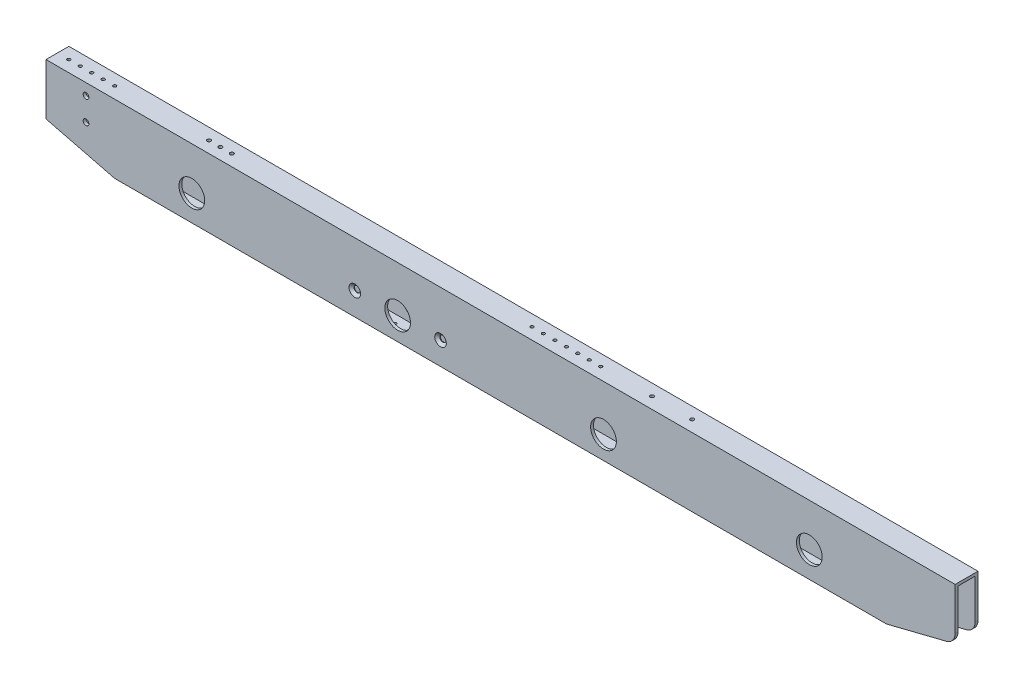
SolidWorks part; units mm, degrees
material "6061-T6 (SS)"
ref_plane "Front Plane" through (0, 0, 0) normal (0, 0, 1) x (1, 0, 0)
ref_plane "Top Plane" through (0, 0, 0) normal (0, 1, 0) x (1, 0, 0)
ref_plane "Right Plane" through (0, 0, 0) normal (1, 0, 0) x (0, 0, -1)
sketch "Sketch1" plane through (0, 0, 0) normal (0, 0, 1) x (1, 0, 0)
  line L0 (0, -12.7) -> (-342.9, -9.525) construction
  line L1 (-504.825, 38.1) -> (504.825, 38.1)
  line L2 (-504.825, 38.1) -> (-504.825, -38.1)
  line L3 (-504.825, -38.1) -> (504.825, -38.1)
  line L4 (504.825, 38.1) -> (504.825, -38.1)
  line L5 (-504.825, 38.1) -> (504.825, -38.1) construction
  line L6 (-504.825, -38.1) -> (504.825, 38.1) construction
  line L7 (-504.825, -38.1) -> (504.825, -38.1) construction
  line L8 (-504.825, -38.1) -> (-504.825, -12.7) construction
  line L9 (-327.025, -63.5) -> (327.025, -63.5) construction
  line L10 (-504.825, -12.7) -> (504.825, -12.7) construction
  line L11 (504.825, -38.1) -> (504.825, -12.7) construction
  line L12 (0, -12.7) -> (342.9, -9.525) construction
  line L13 (-114.3, -12.7) -> (114.3, -12.7) construction
  circle A0 centre (114.3, -12.7) radius 14.2875
  circle A1 centre (-342.9, -9.525) radius 14.2875
  circle A2 centre (342.9, -9.525) radius 14.2875
  circle A3 centre (-114.3, -12.7) radius 14.2875
  point P0 (0, 0)
  dimension "D5" = 28.575
  dimension "D4" = 28.575
  dimension "D8" = 228.6
  dimension "D6" = 228.6
  dimension "D7" = 228.6
  dimension "D1" = 76.2
  dimension "D2" = 1009.65
  dimension "D3" = 25.4
extrude "Boss-Extrude2" add sketch "Sketch1" along normal mid plane 25.4
sketch "Sketch3" plane through (504.825, 0, 0) normal (1, 0, 0) x (0, 0, -1)
  line L8 (9.525, -34.925) -> (9.525, 34.925)
  line L9 (9.525, 34.925) -> (-9.525, 34.925)
  line L10 (-9.525, 34.925) -> (-9.525, -34.925)
  line L11 (-9.525, -34.925) -> (9.525, -34.925)
  line L12 (9.525, -34.925) -> (9.525, 34.925)
  line L13 (9.525, 34.925) -> (-9.525, 34.925)
  line L14 (-9.525, 34.925) -> (-9.525, -34.925)
  line L15 (-9.525, -34.925) -> (9.525, -34.925)
  dimension "D1" = 3.175
extrude "Cut-Extrude2" cut sketch "Sketch3" against normal through all
sketch "Sketch4" plane through (0, 0, 12.7) normal (0, 0, 1) x (1, 0, 0)
  line L0 (-504.825, -38.1) -> (-504.825, -19.05)
  line L1 (-504.825, 38.1) -> (-504.825, -38.1) construction
  line L2 (-504.825, -19.05) -> (-428.625, -38.1)
  line L3 (-504.825, -38.1) -> (504.825, -38.1) construction
  line L4 (-428.625, -38.1) -> (-504.825, -38.1)
  line L5 (0, -38.1) -> (0, 38.1) construction
  line L6 (504.825, 38.1) -> (-504.825, 38.1) construction
  line L7 (428.625, -38.1) -> (504.825, -38.1)
  line L8 (504.825, -38.1) -> (504.825, -19.05)
  line L9 (504.825, -19.05) -> (428.625, -38.1)
  dimension "D1" = 19.05
  dimension "D2" = 76.2
  dimension "D3" = 57.15
extrude "Cut-Extrude3" cut sketch "Sketch4" against normal through all
fillet "Fillet1" radius 12.7 2 edges at (504.825, -19.05, -11.1125) (504.825, -19.05, 11.1125)
sketch "Sketch9" plane through (0, 38.1, 0) normal (0, 1, 0) x (1, 0, 0)
  line L0 (-504.825, -12.7) -> (-504.825, 12.7) construction
  line L1 (0, -12.7) -> (0, 12.7) construction
  line L2 (504.825, -12.7) -> (-504.825, -12.7) construction
  line L3 (504.825, 12.7) -> (-504.825, 12.7) construction
  circle A0 centre (-492.125, 0) radius 1.7272
  circle A1 centre (-441.325, 0) radius 1.7272
  circle A2 centre (-479.425, 0) radius 1.7272
  circle A3 centre (-466.725, 0) radius 1.7272
  circle A4 centre (-454.025, 0) radius 1.7272
  point P2 (-504.825, 0)
  dimension "D1" = 3.4544
  dimension "D2" = 12.7
  dimension "D3" = 4
  dimension "D4" = 2
extrude "Cut-Extrude5" cut sketch "Sketch9" against normal blind 6.35
sketch "Sketch12" plane through (0, 38.1, 0) normal (0, 1, 0) x (1, 0, 0)
  line L0 (504.825, -12.7) -> (504.825, 12.7) construction
  circle A0 centre (98.425, 0) radius 1.7272
  circle A1 centre (85.725, 0) radius 1.7272
  circle A2 centre (73.025, 0) radius 1.7272
  circle A3 centre (60.325, 0) radius 1.7272
  circle A4 centre (47.625, 0) radius 1.7272
  circle A5 centre (34.925, 0) radius 1.7272
  circle A6 centre (22.225, 0) radius 1.7272
  point P2 (504.825, 0)
  dimension "D1" = 3.4544
  dimension "D2" = 406.4
  dimension "D3" = 7
extrude "Cut-Extrude8" cut sketch "Sketch12" against normal blind 5.08
hole_wizard "CSK for 1/4 Flat Head Machine Screw (100)1" positions "Sketch14" profile "Sketch13" countersink size "1/4" standard "ANSI Inch" end condition through all
sketch "Sketch14" plane through (0, 0, 12.7) normal (0, 0, 1) x (1, 0, 0)
  circle A1 centre (-114.3, -12.7) radius 14.2875 construction
  point P0 (-66.675, -12.7)
  point P2 (-161.925, -12.7)
  dimension "D4" = 47.625
  dimension "D3" = 47.625
sketch "Sketch13" plane through (-66.675, -12.7, 12.7) normal (1, 0, 0) x (0, -1, 0)
  line L0 (0, 0) -> (0, 25.4)
  line L1 (0, 25.4) -> (3.3782, 25.4)
  line L2 (3.3782, 25.4) -> (3.3782, 2.5682)
  line L3 (3.3782, 2.5682) -> (6.4389, 0)
  line L5 (6.4389, 0) -> (0, 0)
  line L6 (-3.3782, 2.5682) -> (-6.4389, 0) construction
  line L11 (0, -6.35) -> (0, 107.95) construction
  dimension "Thru Hole Dia." = 6.7564
  dimension "Thru Hole Depth" = 25.4
  dimension "Near C'Sink Dia." = 12.8778
  dimension "Near C'Sink Angle" = 100
sketch "Sketch15" plane through (0, -38.1, 0) normal (0, -1, 0) x (-1, 0, 0)
  line L0 (428.625, 12.7) -> (428.625, -12.7) construction
  circle A0 centre (415.925, 0) radius 1.7272
  circle A1 centre (396.875, 0) radius 1.7272
  circle A2 centre (377.825, 0) radius 1.7272
  circle A3 centre (358.775, 0) radius 1.7272
  circle A4 centre (339.725, 0) radius 1.7272
  circle A5 centre (320.675, 0) radius 1.7272
  circle A6 centre (301.625, 0) radius 1.7272
  circle A7 centre (282.575, 0) radius 1.7272
  circle A8 centre (263.525, 0) radius 1.7272
  circle A9 centre (244.475, 0) radius 1.7272
  circle A10 centre (225.425, 0) radius 1.7272
  circle A11 centre (206.375, 0) radius 1.7272
  circle A12 centre (187.325, 0) radius 1.7272
  circle A13 centre (168.275, 0) radius 1.7272
  circle A14 centre (149.225, 0) radius 1.7272
  circle A15 centre (130.175, 0) radius 1.7272
  circle A16 centre (111.125, 0) radius 1.7272
  circle A17 centre (92.075, 0) radius 1.7272
  circle A18 centre (73.025, 0) radius 1.7272
  circle A19 centre (53.975, 0) radius 1.7272
  circle A20 centre (34.925, 0) radius 1.7272
  circle A21 centre (15.875, 0) radius 1.7272
  circle A22 centre (-3.175, 0) radius 1.7272
  circle A23 centre (-22.225, 0) radius 1.7272
  circle A24 centre (-41.275, 0) radius 1.7272
  circle A25 centre (-60.325, 0) radius 1.7272
  point P2 (428.625, 0)
  dimension "D1" = 3.4544
  dimension "D2" = 12.7
  dimension "D3" = 26
extrude "Cut-Extrude9" cut sketch "Sketch15" against normal blind 6.35
sketch "Sketch16" plane through (0, 0, -12.7) normal (0, 0, -1) x (-1, 0, 0)
  circle A0 centre (114.3, -12.7) radius 17.4625
  dimension "D1" = 34.925
extrude "Cut-Extrude10" cut sketch "Sketch16" against normal blind 3.81
hole_wizard "1/4 (0.25) Diameter Hole1" positions "Sketch19" profile "Sketch18" hole size "1/4" standard "ANSI Inch" end condition through all
sketch "Sketch19" plane through (0, 0, 12.7) normal (0, 0, 1) x (1, 0, 0)
  line L0 (-504.825, 38.1) -> (-504.825, -19.05) construction
  line L1 (-479.425, -25.4) -> (-479.425, 3.7361) construction
  line L2 (-428.625, -38.1) -> (-504.825, -19.05) construction
  line L5 (504.825, 38.1) -> (-504.825, 38.1) construction
  point P0 (-460.375, 25.4)
  point P2 (-460.375, 0)
  dimension "D1" = 19.05
  dimension "D2" = 25.4
  dimension "D3" = 25.4
  dimension "D4" = 12.7
sketch "Sketch18" plane through (-460.375, 25.4, 12.7) normal (1, 0, 0) x (0, -1, 0)
  line L0 (0, 0) -> (0, 25.4)
  line L1 (0, 25.4) -> (3.175, 25.4)
  line L2 (3.175, 25.4) -> (3.175, 0)
  line L5 (3.175, 0) -> (0, 0)
  line L11 (0, -6.35) -> (0, 107.95) construction
  dimension "Thru Hole Dia." = 6.35
  dimension "Thru Hole Depth" = 25.4
hole_wizard "#10-32 Tapped Hole2" positions "Sketch21" profile "Sketch20" tap size "#10-32" standard "ANSI Inch"
sketch "Sketch21" plane through (0, 38.1, 0) normal (0, 1, 0) x (1, 0, 0)
  circle A0 centre (60.325, 0) radius 1.7272 construction
  point P0 (155.575, 0)
  point P2 (200.025, 0)
  dimension "D1" = 95.25
  dimension "D2" = 44.45
cosmetic thread "Hole Thread1" parameters "D1"=3.175, "D2"=4.826
cosmetic thread "Hole Thread2" parameters "D1"=3.175, "D2"=4.826
sketch "Sketch20" plane through (155.575, 38.1, 0) normal (1, 0, 0) x (0, 0, 1)
  line L0 (0, 0) -> (0, 14.9293)
  line L1 (0, 14.9293) -> (2.0193, 13.716)
  line L2 (2.0193, 13.716) -> (2.0193, 0)
  line L5 (2.0193, 0) -> (0, 0)
  line L10 (0, 14.9293) -> (-2.0193, 13.716) construction
  line L11 (0, -6.35) -> (0, 107.95) construction
  dimension "Tap Drill Dia." = 4.0386
  dimension "Tap Drill Depth" = 13.716
  dimension "Drill Angle" = 118
hole_wizard "#10-32 Tapped Hole3" positions "Sketch23" profile "Sketch22" tap size "#10-32" standard "ANSI Inch" end condition through all
sketch "Sketch23" plane through (0, 38.1, 0) normal (0, 1, 0) x (1, 0, 0)
  line L0 (-504.825, -12.7) -> (-504.825, 12.7) construction
  point P0 (-336.55, 0)
  point P2 (-311.15, 0)
  point P4 (-323.85, 0)
  dimension "D1" = 168.275
  dimension "D2" = 12.7
  dimension "D3" = 12.7
sketch "Sketch22" plane through (-336.55, 38.1, 0) normal (1, 0, 0) x (0, 0, 1)
  line L0 (0, 0) -> (0, 76.2)
  line L1 (0, 76.2) -> (2.0193, 76.2)
  line L2 (2.0193, 76.2) -> (2.0193, 0)
  line L5 (2.0193, 0) -> (0, 0)
  line L11 (0, -6.35) -> (0, 107.95) construction
  dimension "Thread Major Dia." = 4.0386
  dimension "Thru Tap Drill Depth" = 76.2
